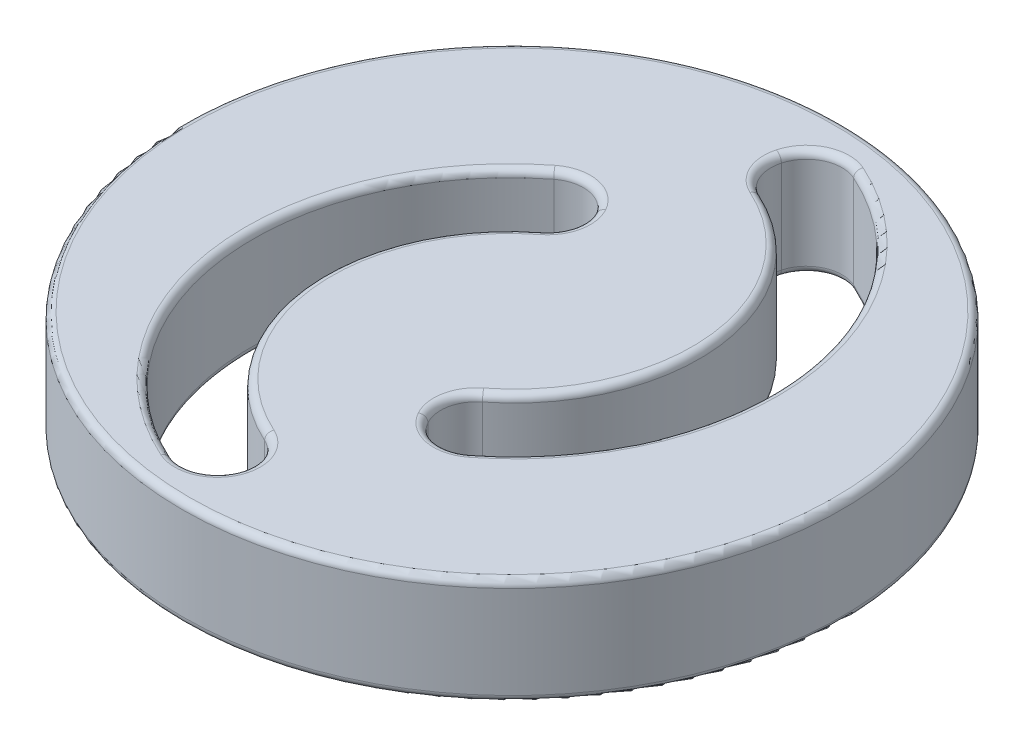
SolidWorks part; units mm, degrees
ref_plane "前视基准面" through (0, 0, 0) normal (0, 0, 1) x (1, 0, 0)
ref_plane "上视基准面" through (0, 0, 0) normal (0, 1, 0) x (1, 0, 0)
ref_plane "右视基准面" through (0, 0, 0) normal (1, 0, 0) x (0, 0, -1)
other "Configuration Table"
sketch "草图1" plane through (0, 0, 0) normal (0, 1, 0) x (1, 0, 0)
  circle A0 centre (0, 0) radius 92.5
  circle A1 centre (0, 0) radius 4
  dimension "D1" = 8
  dimension "D2" = 185
extrude "凸台-拉伸1" add sketch "草图1" along normal blind 30
sketch "草图2" plane through (0, 30, 0) normal (0, 1, 0) x (1, 0, 0)
  line L0 (0, 0) -> (0, 150) construction
  line L1 (0, 0) -> (-60.6659, 166.6783) construction
  line L2 (2.5913, 86.2584) -> (-2.5913, 66.9416)
  line L3 (8.8813, -28.8148) -> (18.4803, -46.3606)
  line L6 (-8.8813, 28.8148) -> (-18.4803, 46.3606)
  line L7 (-2.5913, -86.2584) -> (2.5913, -66.9416)
  arc A0 (0, 76.6) -> (13.6808, -37.5877) centre (-16.0537, 16.7632) cw construction
  arc A1 (-2.5913, 66.9416) -> (8.8813, -28.8148) centre (-16.0537, 16.7632) cw
  arc A2 (2.5913, 86.2584) -> (18.4803, -46.3606) centre (-16.0537, 16.7632) cw
  arc A3 (-2.5913, 66.9416) -> (8.8813, -28.8148) centre (-16.0537, 16.7632) cw construction
  arc A5 (0, 76.6) -> (13.6808, -37.5877) centre (-16.0537, 16.7632) cw construction
  arc A8 (-2.5913, -86.2584) -> (-18.4803, 46.3606) centre (16.0537, -16.7632) cw
  arc A9 (2.5913, -66.9416) -> (-8.8813, 28.8148) centre (16.0537, -16.7632) cw
  arc A10 (0, -76.6) -> (-13.6808, 37.5877) centre (16.0537, -16.7632) cw construction
  point P3 (0, 0)
  point P20 (0, 0)
  point P27 (0, 0)
  point P30 (1.3102, 1.6636)
  dimension "D1" = 20
  dimension "D2" = 76.6
  dimension "D3" = 40
  dimension "D4" = 10
  dimension "D5" = 10
  dimension "D6" = 2
extrude "切除-拉伸1" cut sketch "草图2" against normal blind 30
fillet "圆角3" radius 10 8 edges at (-18.4803, 15, -46.3606) (-8.8813, 15, -28.8148) (-2.5913, 15, 86.2584) (2.5913, 15, 66.9416) (18.4803, 15, 46.3606) (8.8813, 15, 28.8148) (-2.5913, 15, -66.9416) (2.5913, 15, -86.2584)
extrude "凸台-拉伸2" add sketch "草图1<3>" along normal up to surface (30 mm away) contours A1 region at (0, 0, 0) up to face at (-21.468, 30, 21.2587)
sketch "草图1<3>" plane through (0, 0, 0) normal (0, 1, 0) x (1, 0, 0) same geometry as "草图1"
fillet "圆角4" radius 2 26 edges at (0, 0, 92.5) (20.0405, 0, 41.8686) (12.2707, 0, 30.0522) (35.5303, 0, -22.9435) (0.4099, 0, -68.9446) (5.1685, 0, -82.2621) (55.3883, 0, -25.3227) (-55.3883, 0, 25.3227) (-20.0405, 0, -41.8686) (-12.2707, 0, -30.0522) (-35.5303, 0, 22.9435) (-0.4099, 0, 68.9446) (-5.1685, 0, 82.2621) (0, 30, 92.5) (35.5303, 30, -22.9435) (12.2707, 30, 30.0522) (20.0405, 30, 41.8686) (55.3883, 30, -25.3227) (5.1685, 30, -82.2621) (0.4099, 30, -68.9446) (-12.2707, 30, -30.0522) (-20.0405, 30, -41.8686) (-55.3883, 30, 25.3227) (-5.1685, 30, 82.2621) (-0.4099, 30, 68.9446) (-35.5303, 30, 22.9435)
extrude "凸台-拉伸3" add sketch "草图1<4>" against normal blind 15 contours A1 region at (0, 0, 0)
sketch "草图1<4>" plane through (0, 0, 0) normal (0, 1, 0) x (1, 0, 0) same geometry as "草图1"
fillet "圆角5" radius 2 2 edges at (0, -15, 4) (0, 0, 4)
